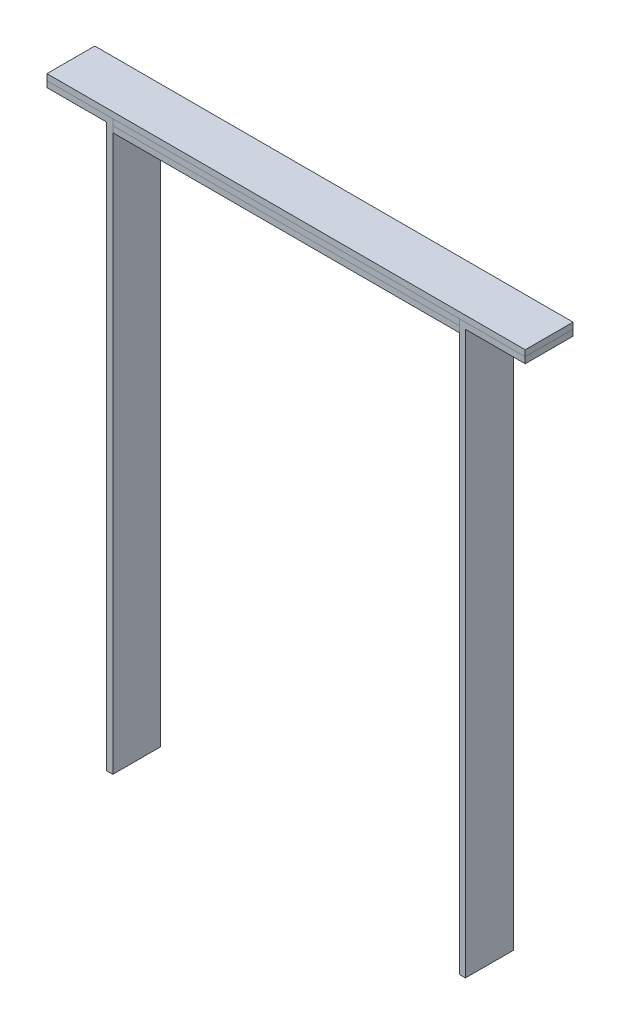
SolidWorks part; units mm, degrees
ref_plane "Front Plane" through (0, 0, 0) normal (0, 0, 1) x (1, 0, 0)
ref_plane "Top Plane" through (0, 0, 0) normal (0, 1, 0) x (1, 0, 0)
ref_plane "Right Plane" through (0, 0, 0) normal (1, 0, 0) x (0, 0, -1)
sketch "Sketch2" plane through (0, 0, 0) normal (0, 0, 1) x (1, 0, 0)
  line L0 (0, 0) -> (0, 117.46)
  line L1 (0, 117.46) -> (-12.5, 117.46)
  line L2 (-12.5, 117.46) -> (-12.5, 118.73)
  line L3 (-12.5, 118.73) -> (1.27, 118.73)
  line L4 (1.27, 118.73) -> (1.27, 0)
  line L5 (1.27, 0) -> (0, 0)
  line L6 (-12.5, 118.73) -> (-12.5, 120)
  line L7 (-12.5, 120) -> (87.5, 120)
  line L8 (87.5, 120) -> (87.5, 118.73)
  line L9 (87.5, 118.73) -> (-12.5, 118.73)
  line L10 (87.5, 118.73) -> (87.5, 117.46)
  line L11 (87.5, 117.46) -> (75, 117.46)
  line L12 (75, 117.46) -> (75, 0)
  line L13 (75, 0) -> (73.73, 0)
  line L14 (73.73, 0) -> (73.73, 118.73)
  line L15 (73.73, 118.73) -> (87.5, 118.73)
  line L17 (1.27, 118.73) -> (73.73, 118.73)
  line L18 (1.27, 118.73) -> (1.27, 117.46)
  line L19 (1.27, 117.46) -> (73.73, 117.46)
  line L20 (73.73, 118.73) -> (73.73, 117.46)
  line L21 (1.27, 117.46) -> (73.73, 117.46)
  line L22 (1.27, 117.46) -> (1.27, 116.19)
  line L23 (1.27, 116.19) -> (73.73, 116.19)
  line L24 (73.73, 117.46) -> (73.73, 116.19)
  dimension "D1" = 1.27
  dimension "D2" = 1.27
  dimension "D3" = 100
  dimension "D4" = 12.5
  dimension "D5" = 120
  dimension "D6" = 1.27
extrude "Boss-Extrude1" add sketch "Sketch2" along normal blind 10 contours L5 L4 L3 L2 L1 L0 | L14 L13 L12 L11 L10 L9 region at (1.1953, 58.73, 0) region at (74.9253, 116.825, 0)
extrude "Boss-Extrude2" add sketch "Sketch2<4>" along normal blind 10 separate body contours L4 L19 L14 L9 region at (37.5, 118.095, 0)
sketch "Sketch2<4>" plane through (0, 0, 0) normal (0, 0, 1) x (1, 0, 0) same geometry as "Sketch2"
extrude "Boss-Extrude3" add sketch "Sketch2<5>" along normal blind 10 separate body contours L9 L8 L7 L6 L3 region at (37.5, 119.365, 0)
sketch "Sketch2<5>" plane through (0, 0, 0) normal (0, 0, 1) x (1, 0, 0) same geometry as "Sketch2"
extrude "Boss-Extrude4" add sketch "Sketch2<7>" along normal blind 10 separate body contours L4 L23 L14 L19 region at (37.5, 116.825, 0)
sketch "Sketch2<7>" plane through (0, 0, 0) normal (0, 0, 1) x (1, 0, 0) same geometry as "Sketch2"
